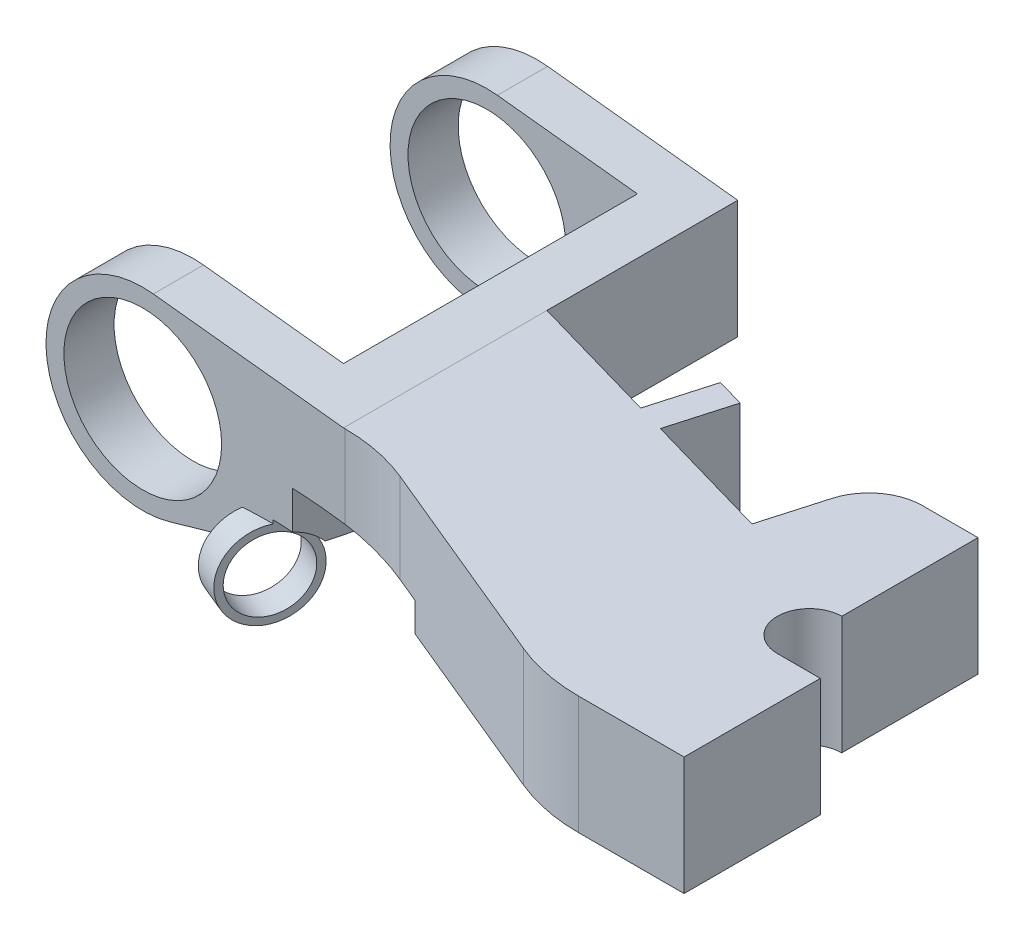
SolidWorks part; units mm, degrees
ref_plane "Спереди" through (0, 0, 0) normal (0, 0, 1) x (1, 0, 0)
ref_plane "Сверху" through (0, 0, 0) normal (0, 1, 0) x (1, 0, 0)
ref_plane "Справа" through (0, 0, 0) normal (1, 0, 0) x (0, 0, -1)
sketch "Эскиз8" plane through (0, 0, 0) normal (0, 1, 0) x (1, 0, 0)
  line L0 (-31.6673, 77.5) -> (-62.0836, 77.5) construction
  line L1 (-85, 43.6529) -> (-6, 21) construction
  line L2 (-106, 13.5) -> (-92.5, 13.5)
  line L3 (-92.5, 13.5) -> (-92.5, 6.5)
  line L4 (-92.5, 6.5) -> (-119.5, 6.5)
  line L6 (-119.5, 6.5) -> (-119.5, 13.5)
  line L7 (-119.5, 13.5) -> (-106, 13.5)
  line L8 (-117, 28.0456) -> (-95, 28.0456) construction
  line L31 (-92.5, 61.5) -> (-119.5, 61.5)
  line L32 (-119.5, 61.5) -> (-119.5, 54.5)
  line L33 (-119.5, 54.5) -> (-92.5, 54.5)
  line L34 (-92.5, 54.5) -> (-92.5, 61.5)
  line L37 (-62.0836, 77.5) -> (-62.0836, 61.5) construction
  line L38 (-62.0836, 61.5) -> (-92.5, 61.5) construction
  line L39 (-11.6673, -9.5) -> (-52.0836, -9.5) construction
  line L44 (-52.0836, -9.5) -> (-52.0836, 6.5) construction
  line L45 (-42.6378, 23.1833) -> (-38.3121, 21.943)
  line L46 (-17.6673, 16.0231) -> (-17.6673, 18.5) construction
  line L47 (-52.0836, 6.5) -> (-92.5, 6.5) construction
  line L48 (-106, 28.0456) -> (-85, 28.0456) construction
  line L52 (-92.5, 54.5) -> (-85, 54.5)
  line L53 (-85, 54.5) -> (-85, 13.5)
  line L54 (-85, 13.5) -> (-92.5, 13.5)
  line L56 (-6, 21) -> (-6, 28) construction
  line L59 (-78, 61.5) -> (-78, 63.0226)
  line L60 (-35.418, 32.0362) -> (-39.7436, 33.2766)
  line L61 (-78, 61.5) -> (-78, 33.3233)
  line L64 (-11.6673, 9.5) -> (-17.6673, 9.5)
  line L65 (-17.6673, 37.5) -> (-17.6673, 18.5) construction
  line L67 (-38.3121, 21.943) -> (-35.418, 32.0362)
  line L68 (-41.1218, 28.4703) -> (-42.6378, 23.1833) construction
  line L69 (-60.3189, 28.2533) -> (-57.4247, 38.3465) construction
  line L70 (-39.7436, 33.2766) -> (-41.1218, 28.4703)
  line L71 (-41.1218, 28.4703) -> (-36.7961, 27.2299)
  line L72 (-42.6378, 23.1833) -> (-78, 33.3233)
  line L79 (-38.3121, 21.943) -> (-17.6673, 16.0231) construction
  line L82 (-35.418, 32.0362) -> (-33.8512, 37.5) construction
  line L83 (-57.665, 38.4155) -> (-61.5101, 39.518)
  line L84 (-57.4247, 38.3465) -> (-57.665, 38.4155)
  line L85 (-57.4247, 38.3465) -> (-57.1844, 38.2776)
  line L86 (-57.1844, 38.2776) -> (-60.0786, 28.1844)
  line L87 (-61.5101, 39.518) -> (-62.8883, 34.7117)
  line L88 (-62.8883, 34.7117) -> (-58.5626, 33.4713)
  line L89 (-57.1844, 38.2776) -> (-53.3394, 37.1751)
  line L90 (-53.3394, 37.1751) -> (-56.2335, 27.0818)
  line L91 (-62.8883, 34.7117) -> (-64.4043, 29.4248) construction
  line L92 (-33.8512, 37.5) -> (-17.6673, 37.5) construction
  circle A1 centre (-106, 28.0456) radius 11
  circle A6 centre (-106, 28.0456) radius 13.5
  arc A8 (-17.6673, 18.5) -> (-17.6673, 9.5) centre (-17.6673, 14) ccw
  spline S0 degree 3 poles (-31.6673, 77.5) (-62.0836, 77.5) (-62.0836, 61.5) (-92.5, 61.5) knots 0 0 0 0 1 1 1 1
  spline S1 degree 3 poles (-11.6673, -9.5) (-52.0836, -9.5) (-52.0836, 6.5) (-92.5, 6.5) knots 0 0 0 0 1 1 1 1
  spline S3 degree 2 poles (-35.418, 32.0362) (-33.8512, 37.5) (-17.6673, 37.5) knots 0 0 0 1 1 1
  point P48 (-60.3189, 28.2533)
sketch "Эскиз10" plane through (0, 0, 0) normal (0, 1, 0) x (1, 0, 0)
  line L0 (-34.4146, 72.312) -> (-60.5171, 61.5) construction
  line L2 (-92.5, 61.5) -> (-78, 61.5)
  line L4 (-78, 34.8837) -> (-78, 61.5)
  line L5 (-20.4853, 37.5) -> (-20.4853, 18.5)
  line L9 (-14.4853, 9.5) -> (-14.4853, -9.5)
  line L11 (-34.1789, -9.5) -> (-14.4853, -9.5)
  line L13 (-92.5, 54.5) -> (-85, 54.5)
  line L14 (-85, 54.5) -> (-85, 13.5)
  line L15 (-85, 13.5) -> (-92.5, 13.5)
  line L21 (-92.5, 6.5) -> (-72.8063, 6.5)
  line L22 (-14.4853, 9.5) -> (-20.4853, 9.5)
  line L23 (-20.4853, 9.5) -> (-20.4853, 18.5) construction
  line L24 (-35.418, 32.0362) -> (-37.8987, 23.3849)
  line L27 (-59.6651, 29.6263) -> (-57.1844, 38.2776)
  line L28 (-57.1844, 38.2776) -> (-53.3394, 37.1751)
  line L29 (-53.3394, 37.1751) -> (-55.8201, 28.5237)
  line L31 (-53.4926, -9.5) -> (-53.4926, 6.5) construction
  line L32 (-92.5, 61.5) -> (-119.5, 61.5)
  line L34 (-92.5, 54.5) -> (-119.5, 54.5)
  line L35 (-119.5, 61.5) -> (-119.5, 54.5)
  line L36 (-92.5, 13.5) -> (-119.5, 13.5)
  line L38 (-92.5, 6.5) -> (-119.5, 6.5)
  line L39 (-119.5, 13.5) -> (-119.5, 6.5)
  line L40 (-78, 34.8837) -> (-59.6651, 29.6263)
  line L41 (-53.4926, -1.5) -> (-72.8063, 6.5)
  line L42 (-53.4926, -1.5) -> (-34.1789, -9.5)
  line L43 (-55.8201, 28.5237) -> (-37.8987, 23.3849)
  line L44 (-20.4853, 37.5) -> (-28.1673, 37.5)
  line L45 (-35.418, 32.0362) -> (-28.1673, 29.9571) construction
  line L46 (-28.1673, 37.5) -> (-28.1673, 29.9571) construction
  arc A0 (-20.4853, 18.5) -> (-20.4853, 9.5) centre (-20.4853, 14) ccw
  arc A2 (-35.418, 32.0362) -> (-28.1673, 37.5) centre (-28.1673, 29.9571) cw
extrude "Бобышка-Вытянуть1" add sketch "Эскиз10" along normal mid plane 27 separate body contours L24 L29 L28 L27 L4 L32 L35 L34 L13 L14 L15 L36 L39 L38 region at (-59.1919, 0, -19.6134)
sketch "Эскиз11" plane through (0, 0, 0) normal (0, 0, 1) x (1, 0, 0)
  line L10 (-11.6673, -6) -> (-11.6673, 10.5)
  line L16 (-106, 0) -> (-11.6673, 0) construction
  line L31 (-11.6673, 10.5) -> (-78, 10.5)
  line L50 (-119.5, 13.5) -> (-11.6673, 13.5)
  line L51 (-119.5, 13.5) -> (-119.5, -13.5)
  line L52 (-119.5, -13.5) -> (-11.6673, -13.5)
  line L53 (-11.6673, 13.5) -> (-11.6673, -13.5)
  line L55 (-78, 10.5) -> (-78, -6)
  line L56 (-78, -6) -> (-11.6673, -6)
  line L57 (-78, -6) -> (-102.2714, -12.9749)
  line L58 (-78, 10.5) -> (-104.5232, 13.419)
  circle A2 centre (-106, 0) radius 11
  circle A5 centre (-106, 0) radius 13.5
extrude "Вырез-Вытянуть1" cut sketch "Эскиз11" against normal through all both and the other way through all contours A2 | A5 L51 L52 | A5 L50 L51 | L52 L53 | L50 L53 region at (-51.7306, -9.9565, 0) region at (-52.0379, 12.0853, 0) region at (-116.4845, -10.4845, 0) region at (-116.4845, 10.4845, 0) region at (-106, 0, 0)
sketch "Эскиз12" plane through (-62.9818, 0, -18.0597) normal (-0.9613, 0, -0.2756) x (-0.2756, 0, 0.9613)
  line L0 (-18.5327, 0) -> (-18.5327, -6) construction
  line L1 (-21.0327, 0) -> (-18.5327, 0) construction
  line L2 (-21.0327, -6) -> (-12.0327, -6) construction
  circle A0 centre (-18.5327, 0) radius 2.5
extrude "Бобышка-Вытянуть2" add sketch "Эскиз12" along normal blind 4.5
sketch "Эскиз13" plane through (-41.2153, 0, -11.8183) normal (-0.9613, 0, -0.2756) x (-0.2756, 0, 0.9613)
  line L0 (-21.0327, 0) -> (-18.5327, 0) construction
  line L2 (-18.5327, 0) -> (-18.5327, -6) construction
  line L3 (-12.0327, -6) -> (-21.0327, -6) construction
  circle A0 centre (-18.5327, 0) radius 2.5
extrude "Бобышка-Вытянуть3" add sketch "Эскиз13" along normal blind 4.5
fillet "Скругление1" radius 25 2 edges at (-34.1789, 2.25, 9.5) (-72.8063, 2.25, -6.5)
sketch "Эскиз15" plane through (-80.9415, 0, -33.5271) normal (-0.9239, 0, -0.3827) x (-0.3827, 0, 0.9239)
  circle A0 centre (27.9359, -12) radius 5
  circle A1 centre (27.9359, -12) radius 6
extrude "Бобышка-Вытянуть4" add sketch "Эскиз15" against normal blind 4
sketch3d "Трехмерный эскиз2"
  line L0 (-75.2961, -2.5, 5.5433) -> (-82.6968, -2.5, 2.4778)
  line L1 (-82.6968, -2.5, 2.4778) -> (-78.1046, -21.5, -8.6087)
ref_plane "Плоскость3" through (-9.7155, -16.0344, 23.4553) normal (-0.3236, -0.534, 0.7811) x (0.9462, -0.1826, 0.2671)
sketch "Эскиз18" plane through (-9.7155, -16.0344, 23.4553) normal (-0.3236, -0.534, 0.7811) x (0.9462, -0.1826, 0.2671)
  line L0 (-82.0108, -7.1077) -> (-81.0339, -6.8941)
  line L3 (-81.0339, -6.8941) -> (-81.2236, -6.0364)
  line L4 (-83.4754, -7.4316) -> (-83.9636, -7.5396)
  line L5 (-80.5962, -3.4484) -> (-79.6779, -2.2435)
  line L6 (-83.9636, -7.5396) -> (-87.8692, -8.4035) construction
  line L7 (-77.1301, -0.6655) -> (-69.3087, 1.0645)
  line L9 (-62.7353, -0.8951) -> (-62.0049, -4.1972)
  line L18 (-69.4167, 1.5527) -> (-63.0749, 2.9554)
  line L20 (-62.2471, -0.7871) -> (-63.0749, 2.9554)
  line L22 (-69.3087, 1.0645) -> (-69.4167, 1.5527) construction
  line L24 (-62.7353, -0.8951) -> (-62.2471, -0.7871) construction
  line L32 (-62.2471, -0.7871) -> (-61.5167, -4.0892)
  line L39 (-83.4754, -7.4316) -> (-82.0108, -7.1077)
  line L41 (-77.1301, -0.6655) -> (-77.2381, -0.1773) construction
  line L42 (-77.2381, -0.1773) -> (-69.4167, 1.5527)
  line L43 (-73.2194, 0.1995) -> (-73.3274, 0.6877) construction
  line L45 (-77.2381, -0.1773) -> (-82.7615, -1.399)
  line L46 (-81.2236, -6.0364) -> (-81.7118, -6.1443) construction
  line L47 (-83.9636, -7.5396) -> (-84.0716, -7.0514)
  line L48 (-84.0716, -7.0514) -> (-81.6306, -6.5115)
  line L49 (-81.6306, -6.5115) -> (-82.7615, -1.399)
  line L50 (-80.5962, -3.4484) -> (-80.9938, -3.1453) construction
  line L51 (-79.6779, -2.2435) -> (-80.0755, -1.9404) construction
  line L52 (-80.137, -2.8459) -> (-80.5347, -2.5428) construction
  line L53 (-80.9938, -3.1453) -> (-80.0755, -1.9404) construction
  line L54 (-69.3087, 1.0645) -> (-68.5889, -2.1898) construction
  line L55 (-62.7353, -0.8951) -> (-68.5889, -2.1898) construction
  line L56 (-83.9636, -7.5396) -> (-82.6678, -13.398)
  line L57 (-82.6678, -13.398) -> (-60.5403, -8.5037)
  line L58 (-61.5167, -4.0892) -> (-60.5403, -8.5037)
  spline S1 degree 3 poles (-81.2236, -6.0364) (-81.4199, -5.1489) (-81.1996, -4.2401) (-80.5962, -3.4484) knots 0 0 0 0 1 1 1 1 weights 1 0.949253 0.949253 1
  spline S3 degree 3 poles (-79.6779, -2.2435) (-79.0744, -1.4518) (-78.1798, -0.8977) (-77.1301, -0.6655) knots 0 0 0 0 1 1 1 1 weights 1 0.949253 0.949253 1
  spline S5 degree 3 poles (-69.3087, 1.0645) (-65.7664, 1.848) (-63.0107, 1.0266) (-62.7353, -0.8951) knots 0 0 0 0 1 1 1 1 weights 1 0.79515 0.79515 1
revolve "Вырез-Повернуть2" cut sketch "Эскиз18" angle 360 about L57 region at (-78.1506, -7.1809, 1.161)
sketch "Эскиз19" plane through (-77.246, 0, -31.9963) normal (0.9239, 0, 0.3827) x (0.3827, 0, -0.9239)
  line L0 (-33.9359, -2.5) -> (-21.9359, -21.5) construction
  circle A0 centre (-27.9359, -12) radius 5
extrude "Вырез-Вытянуть3" cut sketch "Эскиз19" against normal blind 4
sketch "Эскиз20" plane through (-80.9415, 0, -33.5271) normal (0.9239, 0, 0.3827) x (0.3827, 0, -0.9239)
  line L0 (-33.9359, -2.5) -> (-21.9359, -21.5) construction
  circle A0 centre (-27.9359, -12) radius 5
extrude "Вырез-Вытянуть4" cut sketch "Эскиз20" against normal blind 0.5
